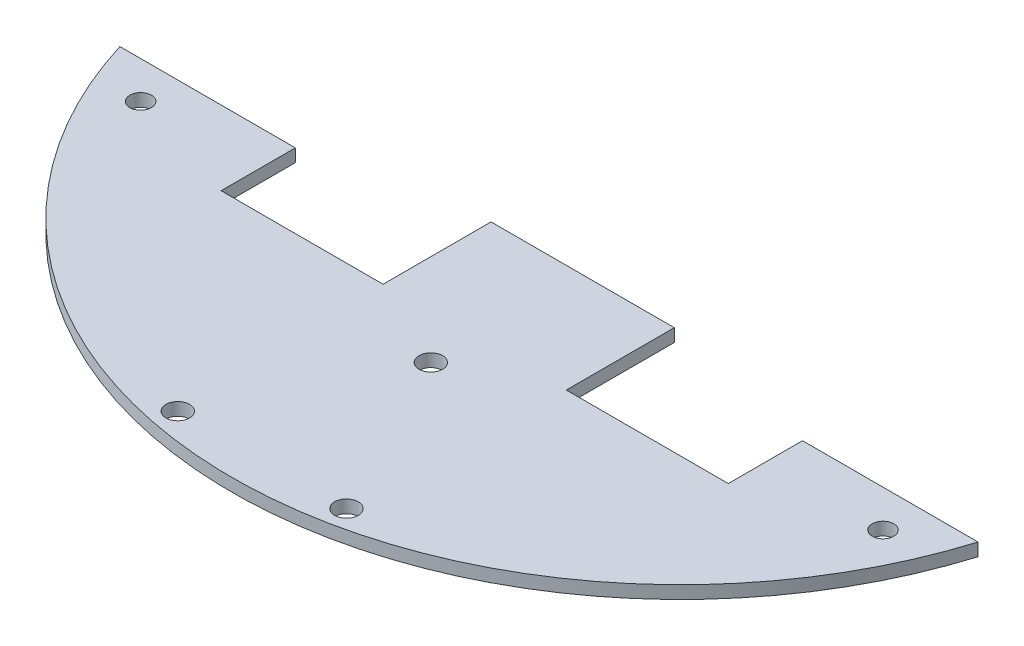
SolidWorks part; units mm, degrees
material "ABS"
ref_plane "Front Plane" through (0, 0, 0) normal (0, 0, 1) x (1, 0, 0)
ref_plane "Top Plane" through (0, 0, 0) normal (0, 1, 0) x (1, 0, 0)
ref_plane "Right Plane" through (0, 0, 0) normal (1, 0, 0) x (0, 0, -1)
sketch "Sketch1" plane through (0, 0, 0) normal (0, 1, 0) x (1, 0, 0)
  line L1 (-18, -10) -> (18, -10)
  line L2 (-18, -10) -> (-18, 10)
  line L3 (-18, 10) -> (18, 10)
  line L4 (18, -10) -> (18, 10)
  line L5 (-18, -10) -> (18, 10) construction
  line L6 (-18, 10) -> (18, -10) construction
  point P0 (0, 0)
  dimension "D1" = 36
  dimension "D2" = 20
extrude "Boss-Extrude1" add sketch "Sketch1" along normal blind 1.9
sketch "Sketch2" plane through (0, 0, 0) normal (0, -1, 0) x (1, 0, 0)
  line L0 (0, -10) -> (0, 10) construction
  line L1 (18, -10) -> (-18, -10) construction
  line L2 (-18, 10) -> (18, 10) construction
sketch "Sketch3" plane through (0, 0, 0) normal (0, -1, 0) x (1, 0, 0)
  line L0 (0, 0) -> (0, 56.5743) construction
  line L1 (-37.5767, 45.5743) -> (-37.5767, 56.5743)
  line L2 (-37.5767, 56.5743) -> (-13.5767, 56.5743)
  line L3 (0, 0) -> (0, -36.2287) construction
  line L4 (-13.5767, 56.5743) -> (-13.5767, 40.5743)
  line L5 (-13.5767, 40.5743) -> (13.5767, 40.5743)
  line L6 (13.5767, 40.5743) -> (13.5767, 56.5743)
  line L7 (37.5767, 45.5743) -> (63.5767, 45.5743)
  line L8 (13.5767, 56.5743) -> (37.5767, 56.5743)
  line L9 (-37.5767, 45.5743) -> (-63.5767, 45.5743)
  line L10 (37.5767, 56.5743) -> (37.5767, 45.5743)
  arc A2 (68.1909, 19.5743) -> (-68.1909, 19.5743) centre (0, 26.0743) ccw construction
  arc A3 (63.5767, 45.5743) -> (-63.5767, 45.5743) centre (0, 26.0743) ccw
  circle A4 centre (0, 26.0743) radius 72.5 construction
  point P14 (-25.5767, 56.5743)
  point P20 (-63.5767, 45.5743)
  point P26 (63.5767, 45.5743)
  dimension "D1" = 2
  dimension "D3" = 5
  dimension "D4" = 52
  dimension "D5" = 26
  dimension "D6" = 16
  dimension "D2" = 24
extrude "Boss-Extrude2" add sketch "Sketch3" against normal blind 1.9
sketch "Sketch5" plane through (0, 1.9, 0) normal (0, 1, 0) x (1, 0, 0)
  line L2 (-29.6163, 16.0438) -> (29.6163, 16.0438)
  line L3 (-29.6163, 16.0438) -> (-29.6163, -16.0438)
  line L4 (-29.6163, -16.0438) -> (29.6163, -16.0438)
  line L5 (29.6163, 16.0438) -> (29.6163, -16.0438)
  line L6 (-29.6163, 16.0438) -> (29.6163, -16.0438) construction
  line L7 (-29.6163, -16.0438) -> (29.6163, 16.0438) construction
extrude "Cut-Extrude2" cut sketch "Sketch5" against normal blind 10
sketch "Sketch8" plane through (0, 1.9, 0) normal (0, 1, 0) x (1, 0, 0)
  line L0 (0, -26.0743) -> (-47.0226, -73.0969) construction
  line L1 (0, -26.0743) -> (0, -92.5743) construction
  line L2 (0, -26.0743) -> (-25.4484, -87.5123) construction
  line L3 (-63.5767, -45.5743) -> (-37.5767, -45.5743) construction
  line L4 (0, -26.0743) -> (47.0226, -73.0969) construction
  line L5 (0, -26.0743) -> (25.4484, -87.5123) construction
  circle A0 centre (0, -26.0743) radius 66.5 construction
  arc A1 (-63.5767, -45.5743) -> (63.5767, -45.5743) centre (0, -26.0743) ccw construction
  dimension "D1" = 45
  dimension "D2" = 67.5
sketch "Sketch9" plane through (0, 1.9, 0) normal (0, 1, 0) x (1, 0, 0)
  line L0 (18.5, -61.5743) -> (11.5, -61.5743)
  line L1 (18.5, -61.5743) -> (18.5, -73.5743)
  line L2 (18.5, -73.5743) -> (11.5, -73.5743)
  line L3 (11.5, -61.5743) -> (11.5, -73.5743)
  line L4 (-11.5, -61.5743) -> (-11.5, -73.5743)
  line L5 (-18.5, -73.5743) -> (-11.5, -73.5743)
  line L6 (-18.5, -61.5743) -> (-18.5, -73.5743)
  line L7 (-18.5, -61.5743) -> (-11.5, -61.5743)
  line L8 (-15, -61.5743) -> (-15, -73.5743) construction
  line L9 (15, -61.5743) -> (15, -73.5743) construction
  line L11 (-15, -67.5743) -> (15, -67.5743) construction
  line L12 (0, -26.0743) -> (0, -92.5743) construction
  line L13 (-18.5, -61.5743) -> (18.5, -61.5743) construction
  line L15 (-18.5, -61.5743) -> (-11.5, -73.5743)
  line L16 (-18.5, -73.5743) -> (-11.5, -61.5743)
  line L17 (11.5, -61.5743) -> (18.5, -73.5743)
  line L18 (18.5, -61.5743) -> (11.5, -73.5743)
  point P17 (0, -67.5743)
  point P28 (-15, -67.5743)
  point P29 (15, -67.5743)
  dimension "D1" = 7
  dimension "D2" = 12
  dimension "D3" = 30
  dimension "D7" = 25
sketch "Sketch10" plane through (0, 1.9, 0) normal (0, 1, 0) x (1, 0, 0)
  line L0 (-12.5, -88.0743) -> (12.5, -88.0743) construction
  line L1 (-13.5767, -40.5743) -> (13.5767, -40.5743) construction
  line L2 (0, -26.0743) -> (0, -92.5743) construction
  circle A0 centre (-12.5, -88.0743) radius 1.75
  circle A1 centre (12.5, -88.0743) radius 1.75
  circle A2 centre (0, -63.0743) radius 1.75
  point P6 (0, -88.0743)
  dimension "D1" = 25
  dimension "D3" = 3.5
  dimension "D4" = 25
  dimension "D2" = 47.5
extrude "Cut-Extrude3" cut sketch "Sketch10" against normal blind 10
sketch "Sketch11" plane through (0, 0, 0) normal (0, -1, 0) x (1, 0, 0)
  line L0 (-37.5767, 45.5743) -> (-37.5767, 56.5743) construction
  line L1 (-63.5767, 45.5743) -> (-37.5767, 45.5743) construction
  line L2 (-55, 51.0743) -> (55, 51.0743) construction
  line L3 (37.5767, 56.5743) -> (37.5767, 45.5743) construction
  circle A0 centre (-55, 51.0743) radius 1.6
  circle A2 centre (55, 51.0743) radius 1.6
  point P6 (0, 0)
  dimension "D1" = 5.5
  dimension "D2" = 3.2
  dimension "D3" = 17.4233
  dimension "D4" = 17.4233
extrude "Cut-Extrude4" cut sketch "Sketch11" against normal blind 4
